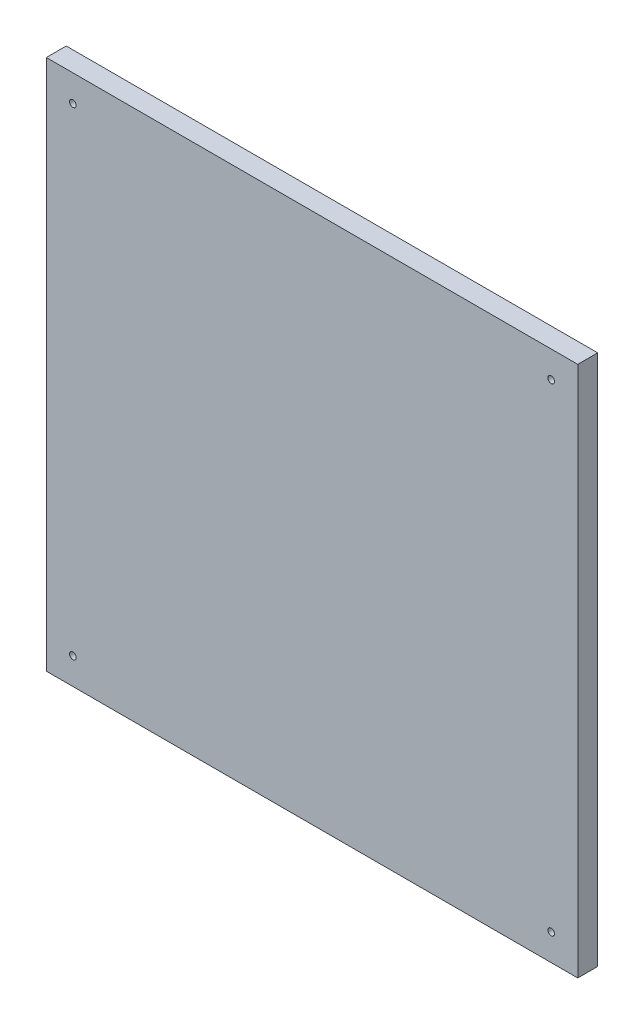
SolidWorks part; units mm, degrees
ref_plane "前视基准面" through (0, 0, 0) normal (0, 0, 1) x (1, 0, 0)
ref_plane "上视基准面" through (0, 0, 0) normal (0, 1, 0) x (1, 0, 0)
ref_plane "右视基准面" through (0, 0, 0) normal (1, 0, 0) x (0, 0, -1)
other "Configuration Table"
sketch "Sketch1" plane through (0, 0, 0) normal (0, 0, 1) x (1, 0, 0)
  line L1 (-400, -400) -> (400, -400)
  line L2 (-400, -400) -> (-400, 400)
  line L3 (-400, 400) -> (400, 400)
  line L4 (400, -400) -> (400, 400)
  line L5 (-400, -400) -> (400, 400) construction
  line L6 (-400, 400) -> (400, -400) construction
  point P0 (0, 0)
extrude "Boss-Extrude1" add sketch "Sketch1" against normal blind 30
sketch "Sketch2" plane through (0, 0, 0) normal (0, 0, 1) x (1, 0, 0)
  circle A0 centre (360, 360) radius 5
extrude "Cut-Extrude1" cut sketch "Sketch2" against normal blind 10
sketch3d "3DSketch1"
  line L0 (360, 360, 0) -> (360, 360, -30) construction
ref_axis "hole_axis_1" through (360, 360, 0) along (0, 0, -1)
sketch "Sketch4" plane through (0, 0, 0) normal (0, 0, 1) x (1, 0, 0)
  circle A0 centre (-360, 360) radius 5
extrude "Cut-Extrude2" cut sketch "Sketch4" against normal blind 10
sketch3d "3DSketch2"
  line L0 (-360, 360, 0) -> (-360, 360, -30) construction
ref_axis "hole_axis_2" through (-360, 360, 0) along (0, 0, -1)
sketch "Sketch6" plane through (0, 0, 0) normal (0, 0, 1) x (1, 0, 0)
  circle A0 centre (-360, -360) radius 5
extrude "Cut-Extrude3" cut sketch "Sketch6" against normal blind 10
sketch3d "3DSketch3"
  line L0 (-360, -360, 0) -> (-360, -360, -30) construction
ref_axis "hole_axis_3" through (-360, -360, 0) along (0, 0, -1)
sketch "Sketch8" plane through (0, 0, 0) normal (0, 0, 1) x (1, 0, 0)
  circle A0 centre (360, -360) radius 5
extrude "Cut-Extrude4" cut sketch "Sketch8" against normal blind 10
sketch3d "3DSketch4"
  line L0 (360, -360, 0) -> (360, -360, -30) construction
ref_axis "hole_axis_4" through (360, -360, 0) along (0, 0, -1)
ref_plane "bottom_face" through (0, 0, -30) normal (0, 0, 1) x (1, 0, 0)
ref_plane "hole_step_face_1" through (0, 0, -10) normal (0, 0, 1) x (1, 0, 0)
